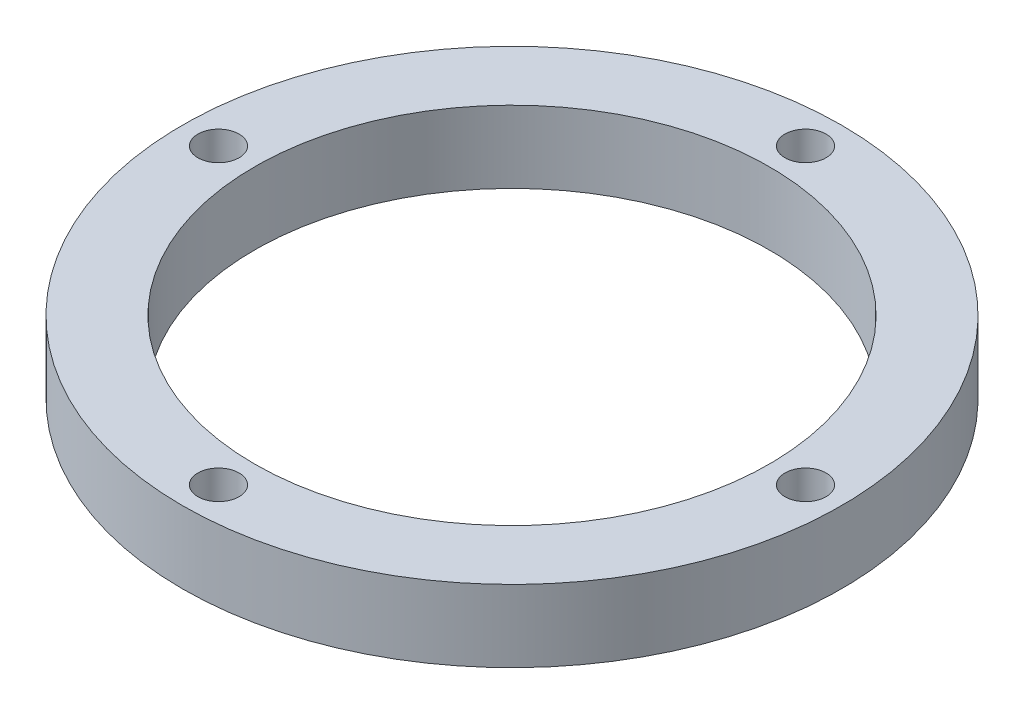
SolidWorks part; units mm, degrees
ref_plane "Front Plane" through (0, 0, 0) normal (0, 0, 1) x (1, 0, 0)
ref_plane "Top Plane" through (0, 0, 0) normal (0, 1, 0) x (1, 0, 0)
ref_plane "Right Plane" through (0, 0, 0) normal (1, 0, 0) x (0, 0, -1)
sketch "Sketch1" plane through (0, 0, 0) normal (0, 1, 0) x (1, 0, 0)
  circle A0 centre (0, 0) radius 25
  circle A1 centre (0, 0) radius 32
  dimension "D1" = 50
  dimension "D2" = 7
extrude "Boss-Extrude1" add sketch "Sketch1" along normal blind 7
sketch "Sketch5" plane through (0, 7, 0) normal (0, 1, 0) x (1, 0, 0)
  circle A0 centre (28.5, 0) radius 2
  circle A1 centre (0, 0) radius 25 construction
  dimension "D1" = 4
  dimension "D2" = 28.5
extrude "Cut-Extrude1" cut sketch "Sketch5" against normal through all
sketch "Sketch7" plane through (0, 0, 0) normal (0, 0, 1) x (1, 0, 0)
  line L0 (0, 0) -> (0, 5.0232) construction
pattern_circular "CirPattern1" count 4 over 360 about axis through (0, 0, 0) along (0, 1, 0) of "Cut-Extrude1" reverse direction yes
